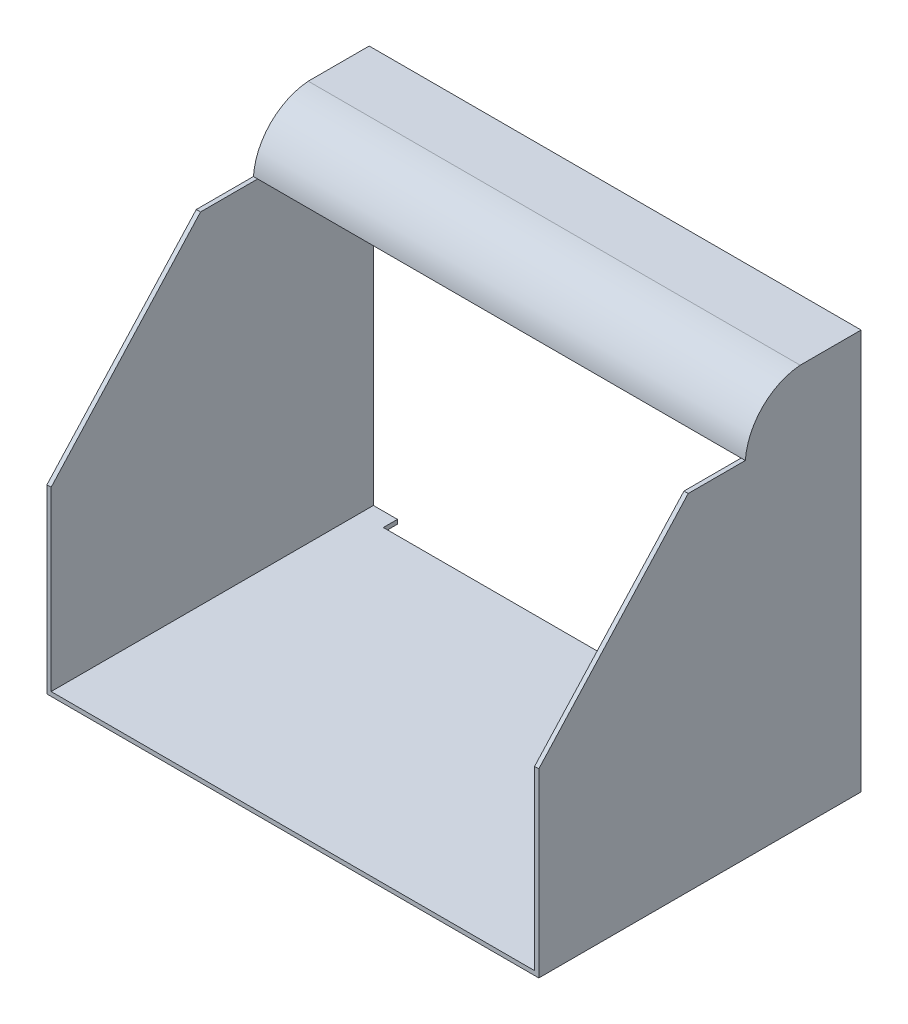
SolidWorks part; units mm, degrees
ref_plane "Front Plane" through (0, 0, 0) normal (1, 0, 0) x (0, 1, 0)
ref_plane "Top Plane" through (0, 0, 0) normal (0, 0, 1) x (0, 1, 0)
ref_plane "Right Plane" through (0, 0, 0) normal (0, 1, 0) x (-1, 0, 0)
sketch "Sketch1" plane through (0, 0, 0) normal (1, 0, 0) x (0, 1, 0)
  line L0 (0, 0) -> (-138.5, 0)
  line L1 (-138.5, 0) -> (-138.5, 111)
  line L2 (-138.5, 111) -> (-76.5, 111)
  line L3 (-76.5, 111) -> (-19.5, 59)
  line L4 (-19.5, 59) -> (-19.5, 38)
  line L5 (0, 20) -> (0, 0)
  line L6 (1.5, 20.0589) -> (1.5, -1.5)
  line L7 (1.5, -1.5) -> (-140, -1.5)
  line L8 (-140, -1.5) -> (-140, 112.5)
  line L9 (-140, 112.5) -> (-75.9186, 112.5)
  line L10 (-75.9186, 112.5) -> (-18, 59.662)
  line L11 (-18, 59.662) -> (-18, 39.4465)
  line L12 (-138.5, 0) -> (-140, 0)
  line L13 (0, 0) -> (1.5, 0)
  arc A0 (-19.5, 38) -> (0, 20) centre (-19.5, 18.4375) cw
  arc A1 (-18, 39.4465) -> (1.5, 20.0589) centre (-19.5, 18.4375) cw
  dimension "D1" = 111
  dimension "D2" = 62
  dimension "D3" = 21
  dimension "D4" = 52
  dimension "D5" = 57
  dimension "D6" = 19.5
  dimension "D7" = 18
  dimension "D8" = 1.5
extrude "Boss-Extrude2" add sketch "Sketch1" along normal blind 174 contours L6 L7 L8 L9 L10 L11 A1
shell "Shell1" thickness 1.5 removed face at (87, -46.9593, 86.081) removed face at (87, -18, 49.5543) removed face at (87, -69.25, -1.5) removed face at (87, -107.9593, 112.5)
sketch "Sketch2" plane through (0, -140, 0) normal (0, -1, 0) x (1, 0, 0)
  line L0 (87, -1.5) -> (87, 112.5) construction
  line L1 (174, -1.5) -> (0, -1.5) construction
  line L2 (174, 112.5) -> (0, 112.5) construction
  line L3 (174, -1.5) -> (174, 112.5) construction
  line L4 (10, -1.5) -> (164, -1.5)
  line L5 (10, -1.5) -> (10, 3.5)
  line L6 (10, 3.5) -> (164, 3.5)
  line L7 (164, -1.5) -> (164, 3.5)
  point P10 (87, 3.5)
  dimension "D1" = 5
  dimension "D2" = 10
extrude "Cut-Extrude1" cut sketch "Sketch2" against normal up to surface (140 mm away) up to face at (87, 0, 9.25)
